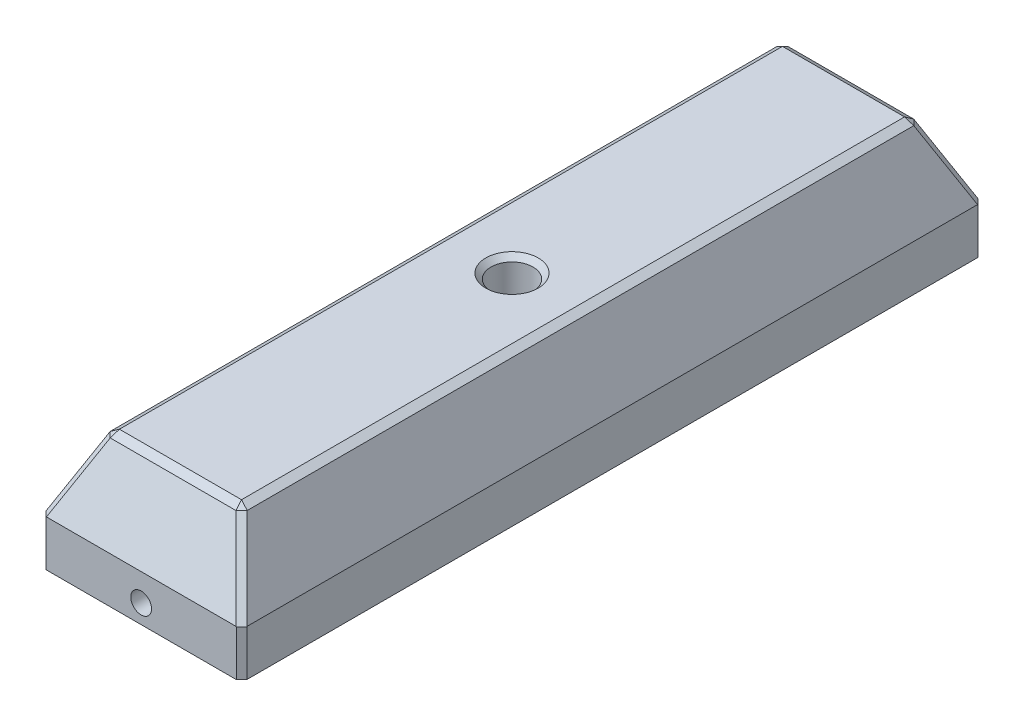
SolidWorks part; units mm, degrees
material "ABS"
ref_plane "正面" through (0, 0, 0) normal (0, 0, 1) x (1, 0, 0)
ref_plane "平面" through (0, 0, 0) normal (0, 1, 0) x (1, 0, 0)
ref_plane "右側面" through (0, 0, 0) normal (1, 0, 0) x (0, 0, -1)
sketch "ｽｹｯﾁ1" plane through (0, 0, 0) normal (0, 0, 1) x (1, 0, 0)
  line L0 (-6.9906, 0) -> (-3.0094, 0)
  line L1 (-3.0094, 0) -> (-1.9906, -2.4)
  line L2 (-1.9906, -2.4) -> (1.9906, -2.4)
  line L3 (0, 0) -> (0, -4.2434) construction
  line L4 (3.0094, 0) -> (1.9906, -2.4)
  line L5 (6.9906, 0) -> (3.0094, 0)
  line L6 (-5, 0) -> (-5, -1.6451) construction
  line L7 (5, 0) -> (5, -1.6451) construction
  line L8 (-6.9906, 0) -> (-8.0094, -2.4)
  line L9 (6.9906, 0) -> (8.0094, -2.4)
  line L10 (-9.6094, -2.4) -> (-8.0094, -2.4)
  line L11 (9.6094, -2.4) -> (8.0094, -2.4)
  line L12 (-9.6094, -2.4) -> (-9.6094, 2)
  line L13 (-9.6094, 2) -> (-6.3452, 9)
  line L14 (-6.3452, 9) -> (6.3452, 9)
  line L15 (6.3452, 9) -> (9.6094, 2)
  line L16 (9.6094, 2) -> (9.6094, -2.4)
  point P8 (0, -2.4)
  point P16 (-5, 0)
  point P18 (5, 0)
  dimension "D1" = 2.4
  dimension "D2" = 10
  dimension "D3" = 23
  dimension "D4" = 2
  dimension "D5" = 1.6
  dimension "D6" = 7
  dimension "D7" = 25
extrude "ﾎﾞｽ - 押し出し1" add sketch "ｽｹｯﾁ1" along normal blind 71
sketch "ｽｹｯﾁ2" plane through (9.6094, 0, 0) normal (1, 0, 0) x (0, 0, -1)
  line L0 (-71, 2) -> (-67.7358, 9)
  line L1 (-71, 9) -> (0, 9) construction
  line L2 (-67.7358, 9) -> (-71, 9)
  line L3 (-71, 9) -> (-71, 2)
  line L4 (-35.5, 9) -> (-35.5, -2.4) construction
  line L5 (-71, -2.4) -> (0, -2.4) construction
  line L6 (-3.2642, 9) -> (0, 9)
  line L7 (0, 2) -> (-3.2642, 9)
  line L8 (0, 9) -> (0, 2)
  dimension "D1" = 25
extrude "ｶｯﾄ - 押し出し1" cut sketch "ｽｹｯﾁ2" against normal through all
chamfer "面取り1" distance 0.5 12 edges at (0, 9, 3.2642) (6.3452, 9, 35.5) (0, 9, 67.7358) (-6.3452, 9, 35.5) (9.6094, -0.2, 71) (-9.6094, -0.2, 71) (-9.6094, -0.2, 0) (9.6094, -0.2, 0) (7.9773, 5.5, 69.3679) (-7.9773, 5.5, 69.3679) (-7.9773, 5.5, 1.6321) (7.9773, 5.5, 1.6321)
sketch "ｽｹｯﾁ3" plane through (0, 0, 71) normal (0, 0, 1) x (1, 0, 0)
  line L0 (-9.1094, 1.9541) -> (-9.1094, -2.4) construction
  line L1 (9.1094, -2.4) -> (-9.1094, -2.4)
  line L2 (9.1094, -2.4) -> (9.1094, 1.9541)
  line L3 (9.1094, 1.9541) -> (-9.1094, 1.9541)
  line L4 (-9.1094, -2.4) -> (-9.1094, 1.9541)
  line L5 (9.1094, -2.4) -> (-9.1094, 1.9541) construction
  line L6 (9.1094, 1.9541) -> (-9.1094, -2.4) construction
  line L8 (-9.1094, -2.4) -> (-8.0094, -2.4) construction
  point P0 (0, -0.223)
extrude "ﾎﾞｽ - 押し出し3" add sketch "ｽｹｯﾁ3" against normal blind 15.5
sketch "ｽｹｯﾁ4" plane through (0, 0, 71) normal (0, 0, 1) x (1, 0, 0)
  line L0 (0, 0) -> (0, -2.4) construction
  line L1 (-9.1094, -2.4) -> (9.1094, -2.4) construction
  circle A0 centre (0, -0.6) radius 0.995
  dimension "D1" = 1.8
  dimension "D2" = 1.99
extrude "ｶｯﾄ - 押し出し2" cut sketch "ｽｹｯﾁ4" against normal blind 12
ref_axis "軸1" through (0, -0.6, 59) along (0, 0, 1)
ref_plane "平面1" through (0, -0.6, 0) normal (0, 1, 0) x (1, 0, 0)
ref_plane "平面2" through (0, 0, 35.5) normal (0, 0, -1) x (-1, 0, 0)
mirror "ﾐﾗｰ1" about plane through (0, 0, 35.5) normal (0, 0, -1) of "ﾎﾞｽ - 押し出し3", "ｶｯﾄ - 押し出し2"
sketch "ｽｹｯﾁ5" plane through (0, -0.6, 0) normal (0, 1, 0) x (1, 0, 0)
  line L0 (0, -59) -> (0, -71) construction
  line L1 (4, -60.75) -> (0, -60.75)
  line L2 (4, -60.75) -> (4, -64.25)
  line L3 (4, -64.25) -> (0, -64.25)
  line L4 (0, -60.75) -> (0, -64.25)
  line L5 (4, -60.75) -> (0, -64.25) construction
  line L6 (4, -64.25) -> (0, -60.75) construction
  line L8 (4, -6.75) -> (0, -6.75)
  line L9 (4, -6.75) -> (4, -10.25)
  line L10 (4, -10.25) -> (0, -10.25)
  line L11 (0, -6.75) -> (0, -10.25)
  line L12 (4, -6.75) -> (0, -10.25) construction
  line L13 (4, -10.25) -> (0, -6.75) construction
  line L14 (1.9906, -55.5) -> (8.0094, -55.5) construction
  line L15 (1.9906, -15.5) -> (8.0094, -15.5) construction
  point P0 (2, -62.5)
  point P7 (2, -8.5)
  dimension "D1" = 7
  dimension "D2" = 3.5
  dimension "D3" = 4
  dimension "D4" = 7
revolve "ｶｯﾄ - 回転1" cut sketch "ｽｹｯﾁ5" angle 360 about axis through (0, -0.6, 59) along (0, 0, 1)
sketch "ｽｹｯﾁ6" plane through (0, -2.4, 0) normal (0, -1, 0) x (1, 0, 0)
  line L0 (0, 0) -> (0, 71) construction
  line L1 (-9.1094, 71) -> (9.1094, 71) construction
  circle A0 centre (0, 35.5) radius 1.5
  dimension "D1" = 3
extrude "ｶｯﾄ - 押し出し3" cut sketch "ｽｹｯﾁ6" against normal through all
sketch "ｽｹｯﾁ7" plane through (0, 9, 0) normal (0, 1, 0) x (1, 0, 0)
  circle A0 centre (0, -35.5) radius 2.01
  dimension "D1" = 4.02
extrude "ｶｯﾄ - 押し出し4" cut sketch "ｽｹｯﾁ7" against normal blind 5
chamfer "面取り2" distance 0.5 angle 45 1 edges at (-2.01, 9, 35.5)
